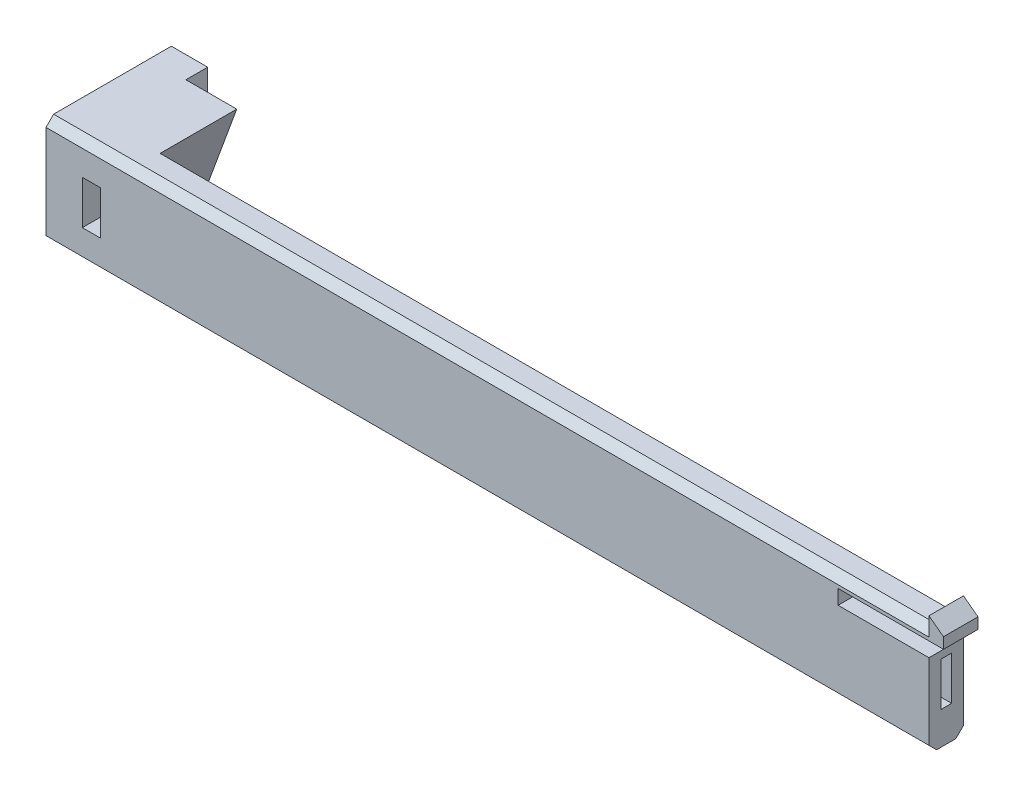
SolidWorks part; units mm, degrees
ref_plane "Front Plane" through (0, 0, 0) normal (0, 0, 1) x (1, 0, 0)
ref_plane "Top Plane" through (0, 0, 0) normal (0, 1, 0) x (1, 0, 0)
ref_plane "Right Plane" through (0, 0, 0) normal (1, 0, 0) x (0, 0, -1)
sketch "Sketch1" plane through (0, 0, 0) normal (0, 0, 1) x (1, 0, 0)
  line L0 (-315, 0) -> (315, 0)
  line L1 (-285.1688, 41.9) -> (-262.5188, 41.9)
  line L2 (-285.1688, 41.9) -> (-285.1688, 21.6)
  line L3 (-285.1688, 21.6) -> (-262.5188, 21.6)
  line L4 (-262.5188, 41.9) -> (-262.5188, 21.6)
  line L5 (262.5187, 41.9) -> (285.1687, 41.9)
  line L6 (262.5187, 41.9) -> (262.5187, 21.6)
  line L7 (262.5187, 21.6) -> (285.1687, 21.6)
  line L8 (285.1687, 41.9) -> (285.1687, 21.6)
  line L9 (-170.8687, 160.7) -> (-148.2188, 160.7)
  line L10 (-170.8687, 160.7) -> (-170.8687, 140.4)
  line L11 (-170.8687, 140.4) -> (-148.2188, 140.4)
  line L12 (-148.2188, 160.7) -> (-148.2188, 140.4)
  line L13 (148.2188, 160.7) -> (170.8688, 160.7)
  line L14 (148.2188, 160.7) -> (148.2188, 140.4)
  line L15 (148.2188, 140.4) -> (170.8688, 140.4)
  line L16 (170.8688, 160.7) -> (170.8688, 140.4)
  line L17 (-273.8438, 31.75) -> (273.8438, 31.75)
  line L18 (-159.5437, 150.55) -> (159.5437, 150.55)
  line L19 (315, 0) -> (315, 30.6)
  line L20 (-248.5188, 79.7) -> (-214.0187, 79.7)
  line L21 (-248.5188, 79.7) -> (-248.5188, 44.9)
  line L22 (-248.5188, 44.9) -> (-214.0187, 44.9)
  line L23 (-214.0187, 79.7) -> (-214.0187, 44.9)
  line L24 (-189.0187, 88.6) -> (-129.3687, 88.6)
  line L25 (-189.0187, 88.6) -> (-189.0187, 48.9)
  line L26 (-189.0187, 48.9) -> (-129.3687, 48.9)
  line L27 (-129.3687, 88.6) -> (-129.3687, 48.9)
  line L28 (-8.5687, 81.6) -> (61.1313, 81.6)
  line L29 (-8.5687, 81.6) -> (-8.5687, 46.9)
  line L30 (-8.5687, 46.9) -> (61.1313, 46.9)
  line L31 (61.1313, 81.6) -> (61.1313, 46.9)
  line L32 (315, 30.6) -> (254, 197)
  line L33 (254, 197) -> (-254, 197)
  line L34 (-254, 197) -> (-315, 30.6)
  line L35 (-315, 30.6) -> (-315, 0)
  line L36 (-315, 4.4515) -> (-244.4143, 197)
  circle A0 centre (-273.8438, 31.75) radius 2.05
  circle A1 centre (273.8438, 31.75) radius 2.05
  circle A2 centre (-159.5437, 150.55) radius 2.05
  circle A3 centre (159.5437, 150.55) radius 2.05
  circle A4 centre (-195.5187, 59.9) radius 2.05
  point P6 (0, 0)
  point P7 (-273.8438, 41.9)
  point P9 (-262.5187, 31.75)
  point P18 (273.8438, 41.9)
  point P19 (285.1688, 31.75)
  point P26 (-159.5437, 160.7)
  point P27 (-148.2188, 150.55)
  point P34 (159.5437, 160.7)
  point P35 (170.8687, 150.55)
  point P36 (0, 31.75)
  point P37 (0, 150.55)
  point P57 (0, 197)
  dimension "D3" = 4.1
  dimension "D7" = 4.1
  dimension "D10" = 4.1
  dimension "D13" = 4.1
  dimension "D18" = 4.1
  dimension "D1" = 22.65
  dimension "D2" = 20.3
  dimension "D4" = 630
  dimension "D5" = 22.65
  dimension "D6" = 20.3
  dimension "D8" = 22.65
  dimension "D9" = 20.3
  dimension "D11" = 22.65
  dimension "D12" = 20.3
  dimension "D14" = 547.6875
  dimension "D15" = 31.75
  dimension "D16" = 98.5
  dimension "D17" = 319.0875
  dimension "D19" = 6.5
  dimension "D20" = 69.7
  dimension "D21" = 34.7
  dimension "D22" = 59.65
  dimension "D23" = 39.7
  dimension "D24" = 34.5
  dimension "D25" = 34.8
  dimension "D26" = 14
  dimension "D27" = 3
  dimension "D28" = 25
  dimension "D29" = 4
  dimension "D30" = 11
  dimension "D31" = 120.8
  dimension "D32" = 2
  dimension "D33" = 30.6
  dimension "D34" = 508
  dimension "D35" = 36.3
  dimension "D36" = 197
  dimension "D37" = 9
sketch "Sketch2" plane through (0, 0, 0) normal (0, 0, 1) x (1, 0, 0)
  line L0 (-315, 0) -> (315, 0) construction
  line L1 (-375, 104) -> (375, 104)
  line L2 (-375, 104) -> (-375, 74)
  line L3 (-375, 74) -> (375, 74)
  line L4 (375, 104) -> (375, 74)
  line L6 (-315, 30.6) -> (-315, 0) construction
  line L7 (315, 0) -> (315, 30.6) construction
  dimension "D1" = 74
  dimension "D2" = 30
  dimension "D3" = 60
  dimension "D4" = 60
sketch "Sketch5" plane through (-8.3611, 207.407, 0) normal (0, 0, 1) x (0.7071, 0.7071, 0)
  line L1 (-321.6588, 154.019) -> (-101.6588, 154.019)
  line L2 (-321.6588, 154.019) -> (-321.6588, -65.981)
  line L3 (-321.6588, -65.981) -> (-101.6588, -65.981)
  line L4 (-101.6588, 154.019) -> (-101.6588, -65.981)
  dimension "D1" = 220
  dimension "D2" = 220
sketch "Sketch3" plane through (0, 0, 0) normal (0, 0, 1) x (1, 0, 0)
  line L0 (-148.2188, 160.7) -> (-148.2188, 140.4) construction
  line L1 (-288.1688, 18.6) -> (-145.2188, 18.6)
  line L2 (-288.1688, 18.6) -> (-288.1688, 163.7)
  line L3 (-288.1688, 163.7) -> (-145.2188, 163.7)
  line L4 (-145.2188, 18.6) -> (-145.2188, 163.7)
  line L5 (-170.8687, 160.7) -> (-148.2188, 160.7) construction
  line L6 (-285.1688, 21.6) -> (-262.5188, 21.6) construction
  line L7 (-285.1688, 41.9) -> (-285.1688, 21.6) construction
  line L8 (-288.1688, 18.6) -> (-289.5045, 74)
  line L9 (-315, 4.4515) -> (-244.4143, 197) construction
  line L10 (-375, 74) -> (375, 74) construction
  line L11 (-289.5045, 74) -> (-256.6217, 163.7)
  line L12 (-173.8687, 163.7) -> (-206.6045, 107)
  line L13 (-285.1688, 21.6) -> (-262.5188, 21.6)
  line L14 (-285.1688, 21.6) -> (-285.1688, 41.9)
  line L15 (-285.1688, 41.9) -> (-262.5188, 41.9)
  line L16 (-262.5188, 21.6) -> (-262.5188, 41.9)
  line L17 (-148.2188, 160.7) -> (-170.8687, 160.7)
  line L18 (-148.2188, 160.7) -> (-148.2188, 140.4)
  line L19 (-148.2188, 140.4) -> (-170.8687, 140.4)
  line L20 (-170.8687, 160.7) -> (-170.8687, 140.4)
  line L21 (-206.6045, 107) -> (-277.4071, 107)
  line L22 (-375, 104) -> (375, 104) construction
  line L23 (-259.5188, 18.6) -> (-259.5188, 71)
  line L24 (-259.5188, 71) -> (-145.2188, 71)
  line L25 (-259.5188, 71) -> (-289.4321, 71)
  line L26 (-206.6045, 107) -> (-145.2188, 107)
  circle A0 centre (-159.5437, 150.55) radius 2.05
  circle A1 centre (-273.8438, 31.75) radius 2.05
  dimension "D1" = 3
  dimension "D2" = 3
  dimension "D3" = 3
  dimension "D4" = 3
  dimension "D5" = 3
  dimension "D6" = 120
  dimension "D7" = 3
  dimension "D8" = 3
  dimension "D9" = 3
sketch "Sketch6" plane through (0, 0, 0) normal (0, 0, 1) x (1, 0, 0)
  line L0 (-375, 104) -> (375, 104) construction
  line L1 (-69.0901, 104) -> (-299.0901, 104)
  line L2 (-69.0901, 104) -> (-69.0901, 74)
  line L3 (-69.0901, 74) -> (-299.0901, 74)
  line L4 (-299.0901, 104) -> (-299.0901, 74)
  line L5 (-375, 74) -> (375, 74) construction
  line L6 (-254, 197) -> (-315, 30.6) construction
  line L9 (-299.0901, 74) -> (-310.0901, 74)
  line L10 (-299.0901, 74) -> (-299.0901, 104)
  line L11 (-299.0901, 104) -> (-310.0901, 104)
  line L12 (-310.0901, 74) -> (-310.0901, 104)
  dimension "D1" = 230
  dimension "D2" = 11
extrude "Boss-Extrude1" add sketch "Sketch6" along normal blind 9.5 contours L1 L4 L3 L2 region at (-184.0901, 89, 0)
sketch "Sketch9" plane through (-299.0901, 0, 0) normal (-1, 0, 0) x (0, 0, 1)
  line L0 (9.5, 104) -> (9.5, 74) construction
  line L1 (3.25, 83) -> (6.25, 83)
  line L2 (3.25, 83) -> (3.25, 95)
  line L3 (3.25, 95) -> (6.25, 95)
  line L4 (6.25, 83) -> (6.25, 95)
  line L5 (9.5, 104) -> (0, 104) construction
  point P4 (6.25, 89)
  point P7 (9.5, 89)
  point P8 (4.75, 95)
  point P11 (4.75, 104)
  dimension "D1" = 3
  dimension "D2" = 12
sketch "Sketch11" plane through (0, 0, 0) normal (0, 0, 1) x (1, 0, 0)
  line L0 (-299.0901, 74) -> (-288.0925, 104)
  line L1 (-254, 197) -> (-315, 30.6) construction
  line L2 (-375, 104) -> (375, 104) construction
  line L3 (-288.0925, 104) -> (-312.0901, 104)
  line L4 (-312.0901, 104) -> (-312.0901, 74)
  line L5 (-375, 74) -> (375, 74) construction
  line L6 (-312.0901, 74) -> (-299.0901, 74)
  dimension "D1" = 13
extrude "Boss-Extrude2" add sketch "Sketch11" along normal up to surface (9.5 mm away) and the other way blind 25 up to face at (-184.0901, 89, 9.5)
sketch "Sketch12" plane through (-312.0901, 0, 0) normal (-1, 0, 0) x (0, 0, 1)
  line L0 (9.5, 104) -> (9.5, 74) construction
  circle A0 centre (1.5, 89) radius 6.5
  point P5 (9.5, 89)
  dimension "D1" = 13
  dimension "D2" = 8
extrude "Cut-Extrude2" cut sketch "Sketch12" against normal blind 2.5
sketch "Sketch13" plane through (0, 0, -25) normal (0, 0, -1) x (-1, 0, 0)
  line L0 (312.0901, 104) -> (312.0901, 74) construction
  line L1 (305.6401, 79) -> (305.6401, 99)
  line L2 (302.0901, 74) -> (302.0901, 104)
  line L3 (375, 74) -> (-375, 74) construction
  line L4 (375, 104) -> (-375, 104) construction
  circle A0 centre (305.6401, 79) radius 1.55
  circle A1 centre (305.6401, 99) radius 1.55
  point P4 (307.1901, 79)
  point P7 (305.6401, 89)
  point P8 (312.0901, 89)
  point P15 (304.0901, 79)
  dimension "D1" = 3.1
  dimension "D2" = 20
  dimension "D3" = 4.9
  dimension "D4" = 2
sketch "Sketch15" plane through (0, 0, 0) normal (0, 0, -1) x (-1, 0, 0)
  line L4 (69.0901, 104) -> (69.0901, 74) construction
  circle A0 centre (152.0901, 89) radius 6.5
  point P7 (69.0901, 89)
  dimension "D1" = 13
  dimension "D2" = 83
extrude "Cut-Extrude3" cut sketch "Sketch15" against normal blind 2.5
sketch "Sketch16" plane through (0, 0, -25) normal (0, 0, -1) x (-1, 0, 0)
  line L0 (302.0901, 74) -> (302.0901, 104)
  line L1 (302.0901, 104) -> (288.0925, 104)
  line L2 (288.0925, 104) -> (299.0901, 74)
  line L3 (299.0901, 74) -> (302.0901, 74)
extrude "Cut-Extrude4" cut sketch "Sketch16" against normal blind 6
sketch "Sketch17" plane through (0, 0, -19) normal (0, 0, -1) x (-1, 0, 0)
  line L0 (302.0901, 74) -> (302.0901, 104) construction
  line L1 (302.0901, 83) -> (297.0901, 83)
  line L2 (302.0901, 83) -> (302.0901, 95)
  line L3 (302.0901, 95) -> (297.0901, 95)
  line L4 (297.0901, 83) -> (297.0901, 95)
  line L6 (299.0901, 83) -> (299.0901, 95) construction
  point P6 (299.0901, 83)
  point P7 (299.0901, 95)
  dimension "D1" = 5
extrude "Cut-Extrude5" cut sketch "Sketch9" against normal through all
extrude "Cut-Extrude6" cut sketch "Sketch17" against normal through all
extrude "Cut-Extrude8" cut sketch "Sketch13" against normal blind 16 contours A0 | A1 region at (-304.5751, 100.065, -25) region at (-306.7052, 80.065, -25)
sketch "Sketch19" plane through (-312.0901, 0, 0) normal (-1, 0, 0) x (0, 0, 1)
  line L0 (-9, 80.55) -> (-9, 77.45) construction
  line L1 (-13.5, 76.2) -> (-16, 76.2)
  line L2 (-13.5, 76.2) -> (-13.5, 81.8)
  line L3 (-13.5, 81.8) -> (-16, 81.8)
  line L4 (-16, 76.2) -> (-16, 81.8)
  line L5 (-16, 96.2) -> (-13.5, 96.2)
  line L6 (-16, 96.2) -> (-16, 101.8)
  line L7 (-16, 101.8) -> (-13.5, 101.8)
  line L8 (-13.5, 96.2) -> (-13.5, 101.8)
  line L9 (-9, 100.55) -> (-9, 97.45) construction
  line L10 (-25, 104) -> (-25, 74) construction
  point P8 (-9, 79)
  point P9 (-9, 99)
  point P12 (-13.5, 79)
  point P16 (-13.5, 99)
  dimension "D1" = 5.6
  dimension "D2" = 2.5
  dimension "D3" = 9
extrude "Cut-Extrude9" cut sketch "Sketch19" against normal blind 10
sketch "Sketch20" plane through (0, 0, 0) normal (0, 0, -1) x (-1, 0, 0)
  line L0 (69.0901, 104) -> (69.0901, 107)
  line L1 (69.0901, 107) -> (65.0901, 104)
  line L2 (375, 104) -> (-375, 104) construction
  line L3 (65.0901, 104) -> (65.0901, 101)
  line L4 (65.0901, 101) -> (94.0901, 101)
  line L5 (94.0901, 101) -> (94.0901, 104)
  line L6 (94.0901, 104) -> (69.0901, 104)
  line L8 (69.0901, 104) -> (69.0901, 74) construction
  line L10 (94.0901, 101) -> (65.0901, 101)
  line L11 (94.0901, 101) -> (94.0901, 97)
  line L12 (94.0901, 97) -> (65.0901, 97)
  line L13 (65.0901, 101) -> (65.0901, 97)
  point P11 (94.0901, 102.5)
  line M12 (69.0901, 104) -> (69.0901, 74)
  dimension "D1" = 3
  dimension "D2" = 4
  dimension "D3" = 25
  dimension "D4" = 3
  dimension "D5" = 4
extrude "Boss-Extrude3" add sketch "Sketch20" against normal up to surface (9.5 mm away) contours L3 L4 L0 L1 M12 region at (-67.3124, 103.3333, 0) up to face at (-299.5901, 89, 9.5)
extrude "Cut-Extrude10" cut sketch "Sketch20<3>" against normal through all contours L12 L11 L4 M12 region at (-81.5901, 99, 0)
sketch "Sketch20<3>" plane through (0, 0, 0) normal (0, 0, -1) x (-1, 0, 0) same geometry as "Sketch20"
chamfer "Chamfer2" distance 2.1 angle 45 4 edges at (-190.5901, 104, 9.5) (-178.5913, 104, 0) (-190.5901, 74, 9.5) (-184.0901, 74, 0)
